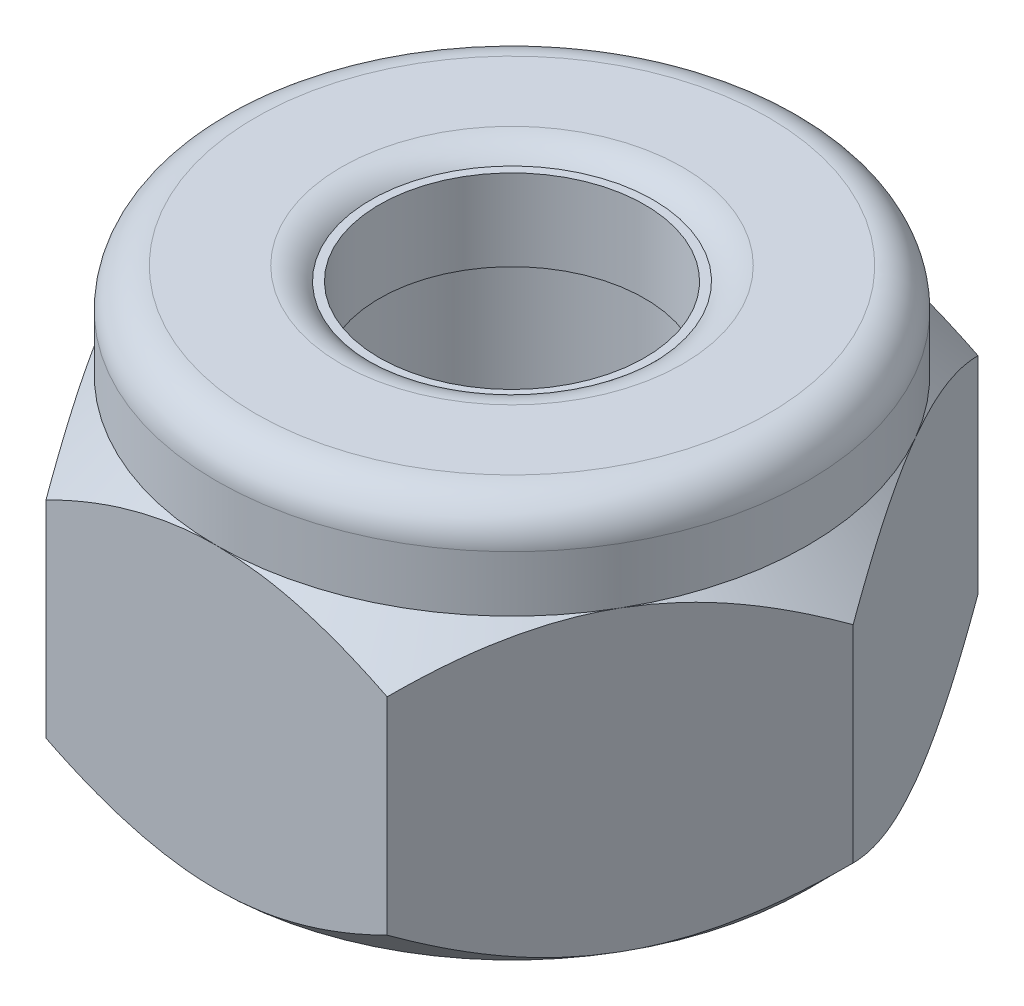
SolidWorks part; units mm, degrees
material "铸造碳钢"
ref_plane "Front" through (0, 0, 0) normal (0, 0, 1) x (1, 0, 0)
ref_plane "Top" through (0, 0, 0) normal (0, 1, 0) x (1, 0, 0)
ref_plane "Right" through (0, 0, 0) normal (1, 0, 0) x (0, 0, -1)
sketch "草图1" plane through (0, 0, 0) normal (0, 1, 0) x (1, 0, 0)
  line L1 (5.0403, 0) -> (2.5201, 4.365)
  line L2 (2.5201, 4.365) -> (-2.5201, 4.365)
  line L3 (-2.5201, 4.365) -> (-5.0403, 0)
  line L4 (-5.0403, 0) -> (-2.5201, -4.365)
  line L5 (-2.5201, -4.365) -> (2.5201, -4.365)
  line L6 (2.5201, -4.365) -> (5.0403, 0)
  circle A0 centre (0, 0) radius 4.365 construction
  dimension "六角对边长" = 8.73
extrude "凸台-拉伸1" add sketch "草图1" along normal mid plane 4.4
sketch "草图3" plane through (0, 2.2, 0) normal (0, 1, 0) x (1, 0, 0)
  circle A0 centre (0, 0) radius 4.365
  dimension "圆形外直径" = 8.73
extrude "凸台-拉伸2" add sketch "草图3" along normal blind 1.4
sketch "草图4" plane through (0, 3.6, 0) normal (0, 1, 0) x (1, 0, 0)
  circle A0 centre (0, 0) radius 2.085
  dimension "螺母内径" = 4.17
extrude "切除-拉伸1" cut sketch "草图4" against normal through all
sketch "草图5" plane through (0, 3.6, 0) normal (0, 1, 0) x (1, 0, 0)
  circle A0 centre (0, 0) radius 2.085
  circle A1 centre (0, 0) radius 1.96
  dimension "橡胶内径" = 3.92
  dimension "橡皮圈外直径" = 4.17
extrude "凸台-拉伸3" add sketch "草图5" against normal up to surface (1.4 mm away) from offset 0.2 up to face at (2.1976, 2.2, 3.8063) offset against normal yes
fillet "圆角1" radius 0.575 2 edges at (0, 3.6, 2.085) (0, 3.6, 4.365)
sketch "草图6" plane through (0, 0, 0) normal (0, 0, 1) x (1, 0, 0)
  line L0 (0, -1000) -> (0, 49000) construction
  line L1 (-1000, 0) -> (49000, 0) construction
  line L2 (-5.0403, 2.2) -> (-5.0403, 1.5247)
  line L3 (-5.0403, 1.5247) -> (-4.365, 2.2)
  line L4 (-4.365, 2.2) -> (-5.0403, 2.2)
  line L5 (0, 2.2) -> (-3.7802, 2.2) construction
  line L6 (-5.0403, 2.2) -> (-5.0403, -2.2) construction
  line L7 (-4.365, -998.4247) -> (-4.365, 49001.5753) construction
  line L8 (-4.365, 3.025) -> (-4.365, 2.2) construction
  line L9 (-5.0403, -2.2) -> (-5.0403, -1.5247)
  line L10 (-5.0403, -1.5247) -> (-4.365, -2.2)
  line L11 (-4.365, -2.2) -> (-5.0403, -2.2)
  dimension "D1" = 45
revolve "切除-旋转1" cut sketch "草图6" angle 360 about L0
sketch "Sketch1" [suppressed] plane through (0, 0, 0) normal (0, 1, 0) x (1, 0, 0)
  circle A0 centre (0, 0) radius 4.305
  dimension "六角外圆直径" = 9.5
extrude "Extrude1" [suppressed] cut sketch "Sketch1" against normal through all both and the other way through all flip side to cut
other "冻结***"
